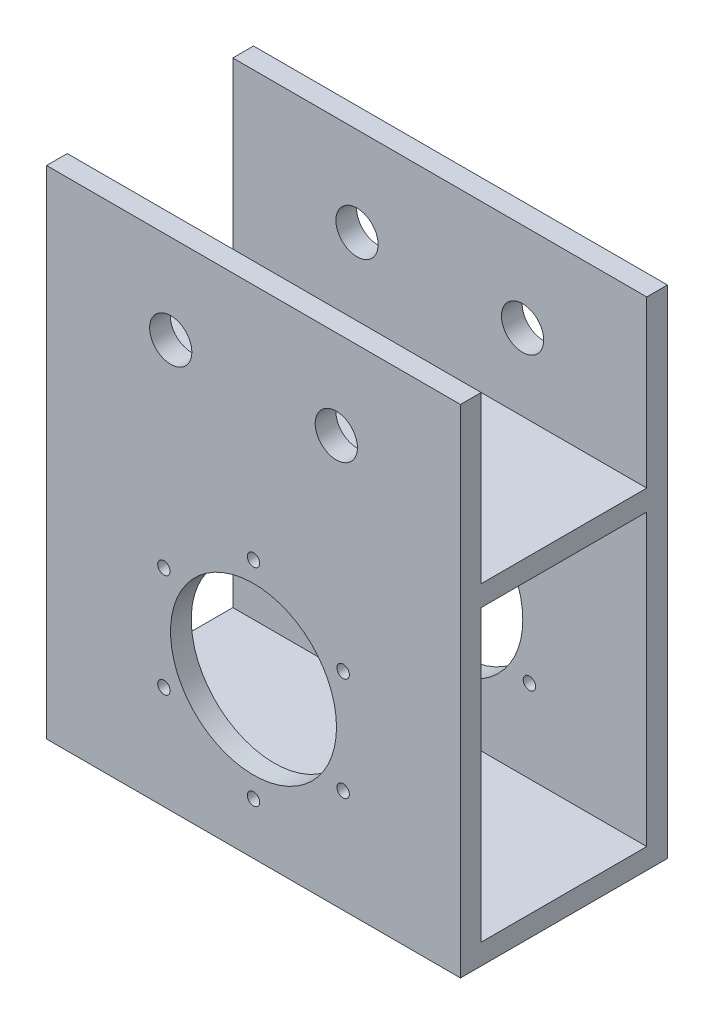
SolidWorks part; units mm, degrees
ref_plane "Front Plane" through (0, 0, 0) normal (0, 0, 1) x (1, 0, 0)
ref_plane "Top Plane" through (0, 0, 0) normal (0, 1, 0) x (1, 0, 0)
ref_plane "Right Plane" through (0, 0, 0) normal (1, 0, 0) x (0, 0, -1)
sketch "Sketch1" plane through (0, 0, 0) normal (0, 0, 1) x (1, 0, 0)
  line L1 (-50, 60) -> (50, 60)
  line L2 (-50, 60) -> (-50, -60)
  line L3 (-50, -60) -> (50, -60)
  line L4 (50, 60) -> (50, -60)
  line L5 (-50, 60) -> (50, -60) construction
  line L6 (-50, -60) -> (50, 60) construction
  point P0 (0, 0)
  dimension "D1" = 100
  dimension "D2" = 120
extrude "Boss-Extrude1" add sketch "Sketch1" along normal blind 5
sketch "Sketch2" plane through (0, 0, 5) normal (0, 0, 1) x (1, 0, 0)
  line L0 (-50, 60) -> (-50, -60) construction
  line L1 (-50, 20) -> (50, 20)
  line L2 (-50, 20) -> (-50, 15)
  line L3 (-50, 15) -> (50, 15)
  line L4 (50, 20) -> (50, 15)
  line L5 (50, -60) -> (50, 60) construction
  line L6 (50, 60) -> (-50, 60) construction
  dimension "D1" = 5
  dimension "D2" = 40
extrude "Boss-Extrude2" add sketch "Sketch2" along normal blind 45
sketch "Sketch3" plane through (0, 20, 0) normal (0, 1, 0) x (1, 0, 0)
  line L0 (50, -50) -> (50, -5) construction
  line L1 (-50, -50) -> (50, -50)
  line L2 (-50, -50) -> (-50, -45)
  line L3 (-50, -45) -> (50, -45)
  line L4 (50, -50) -> (50, -45)
  dimension "D1" = 5
extrude "Boss-Extrude3" add sketch "Sketch3" along normal blind 40 and the other way blind 60
sketch "Sketch6" plane through (0, -40, 0) normal (0, -1, 0) x (1, 0, 0)
  line L1 (-50, 45) -> (50, 45)
  line L2 (-50, 45) -> (-50, 50)
  line L3 (-50, 50) -> (50, 50)
  line L4 (50, 45) -> (50, 50)
  line L5 (-50, 0) -> (50, 0)
  line L6 (-50, 0) -> (-50, 5)
  line L7 (-50, 5) -> (50, 5)
  line L8 (50, 0) -> (50, 5)
extrude "Boss-Extrude4" add sketch "Sketch6" along normal blind 15
sketch "Sketch7" plane through (0, 0, 5) normal (0, 0, 1) x (1, 0, 0)
  line L6 (50, -60) -> (50, 15) construction
  line L7 (-50, -60) -> (50, -60)
  line L8 (-50, -60) -> (-50, -55)
  line L9 (-50, -55) -> (50, -55)
  line L10 (50, -60) -> (50, -55)
  dimension "D1" = 5
extrude "Boss-Extrude5" add sketch "Sketch7" along normal blind 45
sketch "Sketch8" plane through (0, 0, 50) normal (0, 0, 1) x (1, 0, 0)
  line L0 (-50, 15) -> (50, 15) construction
  line L1 (-50, 60) -> (-50, -60) construction
  line L2 (50, -60) -> (50, 60) construction
  line L3 (-50, -60) -> (50, -60) construction
  circle A1 centre (0, -22.5) radius 20.05
  circle A2 centre (0, -22.5) radius 25 construction
  circle A3 centre (0, 2.5) radius 1.5
  circle A4 centre (21.6506, -10) radius 1.5
  circle A5 centre (21.6506, -35) radius 1.5
  circle A6 centre (0, -47.5) radius 1.5
  circle A7 centre (-21.6506, -35) radius 1.5
  circle A8 centre (-21.6506, -10) radius 1.5
  point P26 (0, -22.5)
  dimension "D1" = 40.1
  dimension "D4" = 50
  dimension "D2" = 37.5
  dimension "D3" = 75
extrude "Cut-Extrude1" cut sketch "Sketch8" against normal through all
sketch "Sketch9" plane through (0, 0, 50) normal (0, 0, 1) x (1, 0, 0)
  line L0 (0, 60) -> (0, -60) construction
  line L1 (-50, 60) -> (50, 60) construction
  line L2 (-50, -60) -> (50, -60) construction
sketch "Sketch10" plane through (0, 0, 50) normal (0, 0, 1) x (1, 0, 0)
  line L0 (0, 60) -> (0, -60) construction
  circle A0 centre (-20, 38.4946) radius 5.1
  circle A1 centre (20, 38.4946) radius 5.1
  dimension "D1" = 10.2
  dimension "D2" = 10.2
  dimension "D3" = 40
  dimension "D4" = 20
extrude "Cut-Extrude2" cut sketch "Sketch10" against normal through all
